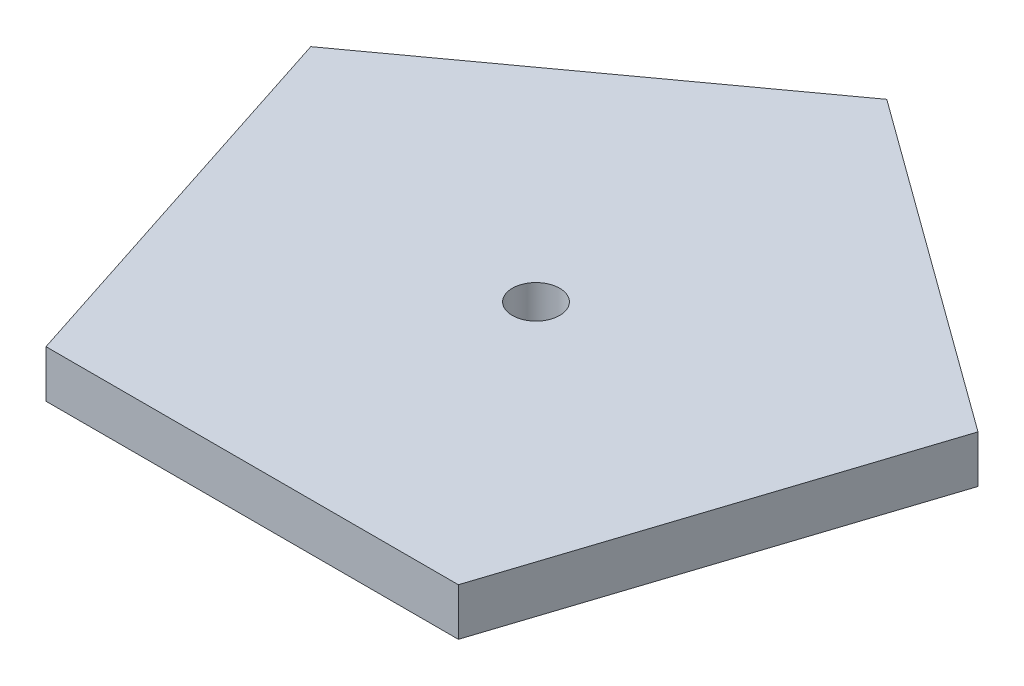
SolidWorks part; units mm, degrees
ref_plane "Front Plane" through (0, 0, 0) normal (0, 0, 1) x (1, 0, 0)
ref_plane "Top Plane" through (0, 0, 0) normal (0, 1, 0) x (1, 0, 0)
ref_plane "Right Plane" through (0, 0, 0) normal (1, 0, 0) x (0, 0, -1)
sketch "Sketch1" plane through (0, 0, 0) normal (0, 1, 0) x (1, 0, 0)
  line L0 (0, -38.1) -> (0, 47.0942) construction
  line L1 (-44.7892, 14.5529) -> (-27.6813, -38.1)
  line L2 (-27.6813, -38.1) -> (27.6813, -38.1)
  line L3 (27.6813, -38.1) -> (44.7892, 14.5529)
  line L4 (44.7892, 14.5529) -> (0, 47.0942)
  line L5 (0, 47.0942) -> (-44.7892, 14.5529)
  line L6 (-44.7892, 14.5529) -> (36.2353, -11.7735) construction
  line L7 (44.7892, 14.5529) -> (-36.2353, -11.7735) construction
  line L8 (-27.6813, -38.1) -> (22.3946, 30.8235) construction
  circle A0 centre (0, 0) radius 38.1 construction
  dimension "D1" = 76.2
extrude "Boss-Extrude1" add sketch "Sketch1" along normal blind 6.35
sketch "Sketch2" plane through (0, 6.35, 0) normal (0, 1, 0) x (1, 0, 0)
  circle A0 centre (0, 0) radius 3.175
  dimension "D1" = 6.35
extrude "Cut-Extrude1" cut sketch "Sketch2" against normal through all
